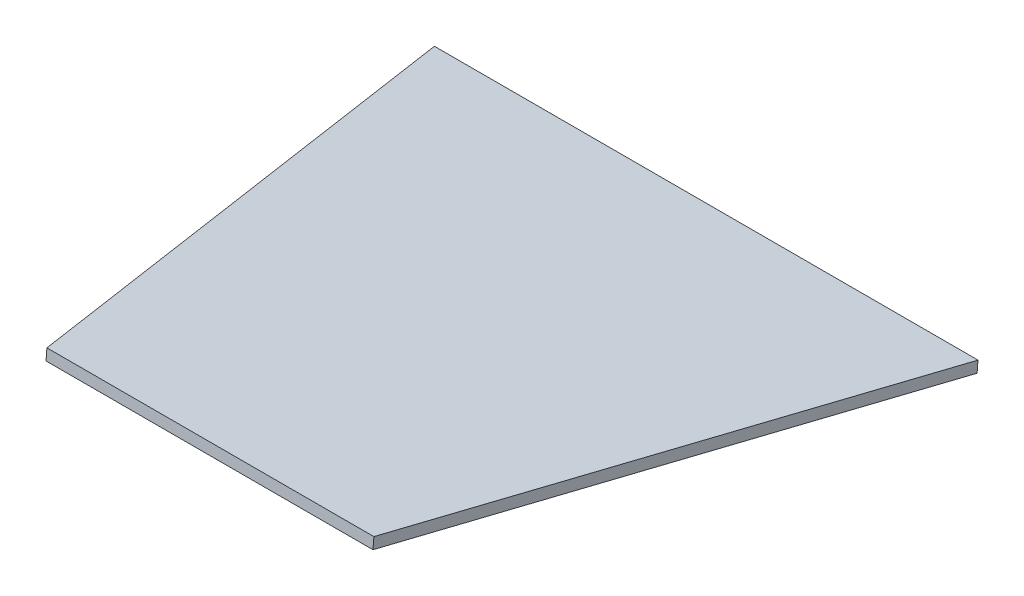
SolidWorks part; units mm, degrees
ref_plane "Front Plane" through (0, 0, 0) normal (0, 0, 1) x (1, 0, 0)
ref_plane "Top Plane" through (0, 0, 0) normal (0, 1, 0) x (1, 0, 0)
ref_plane "Right Plane" through (0, 0, 0) normal (1, 0, 0) x (0, 0, -1)
ref_plane "Plane1" through (-0.0006, -7356.6813, 606.8782) normal (0, -0.9966, 0.0822) x (-1, 0, 0)
sketch "Sketch1" plane through (-0.0006, -7356.6813, 606.8782) normal (0, -0.9966, 0.0822) x (-1, 0, 0)
  line L0 (927.9324, -1893.2884) -> (1306.8393, -1893.2884)
  line L1 (1306.8393, -1893.2884) -> (1432.3521, -1316.7398)
  line L2 (1432.3521, -1316.7398) -> (802.4196, -1316.7398)
  line L3 (802.4196, -1316.7398) -> (927.9324, -1893.2884)
  line L4 (802.4183, -1316.7398) -> (1432.3534, -1316.7398) construction
  line L5 (928.076, -1893.948) -> (801.0629, -1310.5075) construction
  line L6 (1433.7088, -1310.5075) -> (1306.6957, -1893.948) construction
  line L7 (1306.8419, -1893.2884) -> (927.9298, -1893.2884) construction
extrude "Boss-Extrude1" add sketch "Sketch1" along normal blind 12.7
